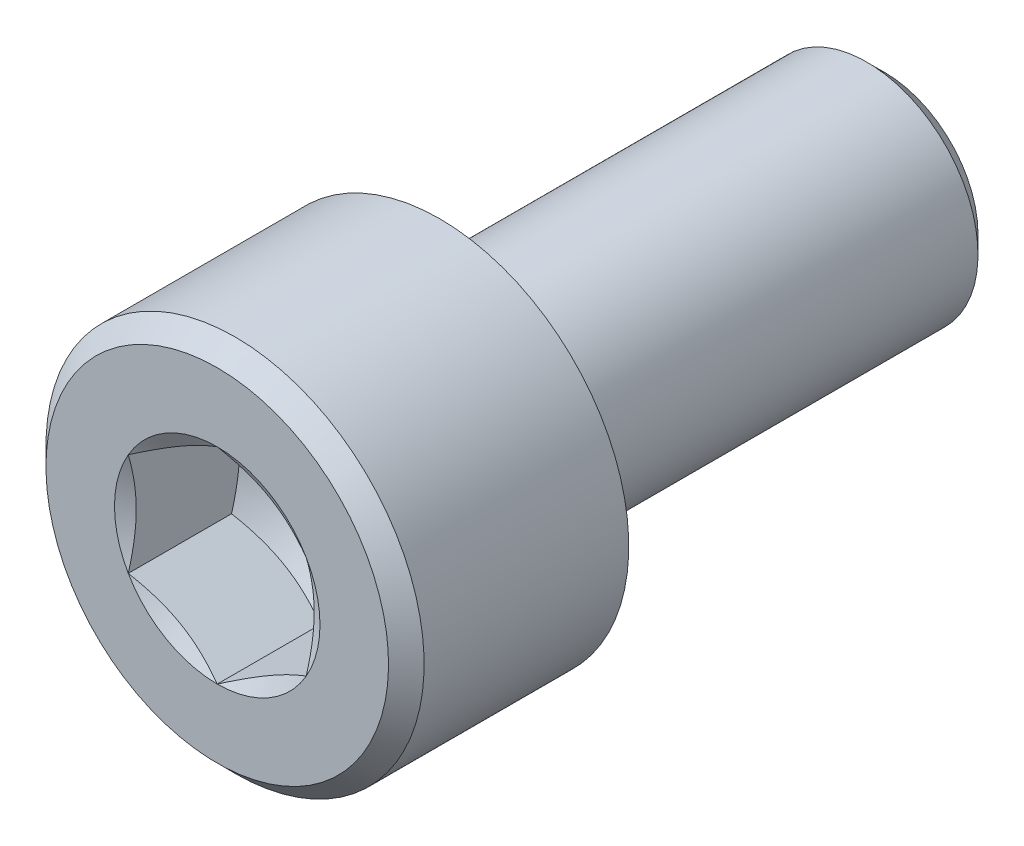
SolidWorks part; units mm, degrees
material "AISI 4130 Steel, annealed at 865C"
ref_plane "Front" through (0, 0, 0) normal (0, 0, 1) x (1, 0, 0)
ref_plane "Top" through (0, 0, 0) normal (0, 1, 0) x (1, 0, 0)
ref_plane "Right" through (0, 0, 0) normal (1, 0, 0) x (0, 0, -1)
sketch "Sketch1" plane through (0, 0, 0) normal (1, 0, 0) x (0, 0, -1)
  line L0 (0, 4.25) -> (-5, 4.25)
  line L1 (-5, 4.25) -> (-5, 0)
  line L2 (-5, 0) -> (10, 0)
  line L3 (10, 0) -> (10, 2.5)
  line L4 (10, 2.5) -> (0, 2.5)
  line L5 (0, 2.5) -> (0, 4.25)
  line L6 (0, 0) -> (12.7561, 0) construction
  dimension "l" = 10
  dimension "d" = 5
  dimension "k" = 5
  dimension "dk" = 8.5
revolve "Revolve1" add sketch "Sketch1" angle 360 about L2
sketch "Sketch7" plane through (0, 0, 0) normal (1, 0, 0) x (0, 0, -1)
  line L0 (-6.6396, 0) -> (3.6195, 0) construction
  line L1 (-5, 0) -> (-5, 2)
  line L2 (-5, 4.25) -> (-5, -4.25) construction
  line L3 (-5, 2) -> (-2.5, 2)
  line L4 (-2.5, 2) -> (-1.3453, 0)
  line L6 (-5, 0) -> (-1.3453, 0)
  dimension "D1" = 60
  dimension "S" = 4
  dimension "t" = 2.5
revolve "Cut-Revolve2" cut sketch "Sketch7" angle 360 about L6
chamfer "Chamfer1" distance 0.4 2 edges at (0, -2.5, -10) (0, -4.25, 5)
sketch "Sketch8" plane through (0, 0, 5) normal (0, 0, 1) x (1, 0, 0)
  line L1 (0, 2.3094) -> (-2, 1.1547)
  line L2 (-2, 1.1547) -> (-2, -1.1547)
  line L3 (-2, -1.1547) -> (0, -2.3094)
  line L4 (0, -2.3094) -> (2, -1.1547)
  line L5 (2, -1.1547) -> (2, 1.1547)
  line L6 (2, 1.1547) -> (0, 2.3094)
  circle A0 centre (0, 0) radius 2 construction
  circle A1 centre (0, 0) radius 2 construction
extrude "Cut-Extrude1" cut sketch "Sketch8" against normal up to surface (2.3214 mm away) up to face at (2, 0, 2.5)
sketch "Sketch9" plane through (0, 0, 0) normal (1, 0, 0) x (0, 0, -1)
  line L0 (-5, 2) -> (4.2695, 2) construction
  line L3 (-5.5, 3.1754) -> (-5.5, 2)
  line L4 (-5.5, 2) -> (-4.8214, 2)
  line L5 (-4.8214, 2) -> (-5.5, 3.1754)
  line L6 (-5, 4.25) -> (-5, -4.25) construction
  dimension "D1" = 60
  dimension "D2" = 0.5
revolve "Cut-Revolve3" cut sketch "Sketch9" angle 360 about axis through (0, 0, 5) along (0, 0, -1)
fillet "Fillet2" radius 0.2 1 edges at (0, -2.5, 0)
